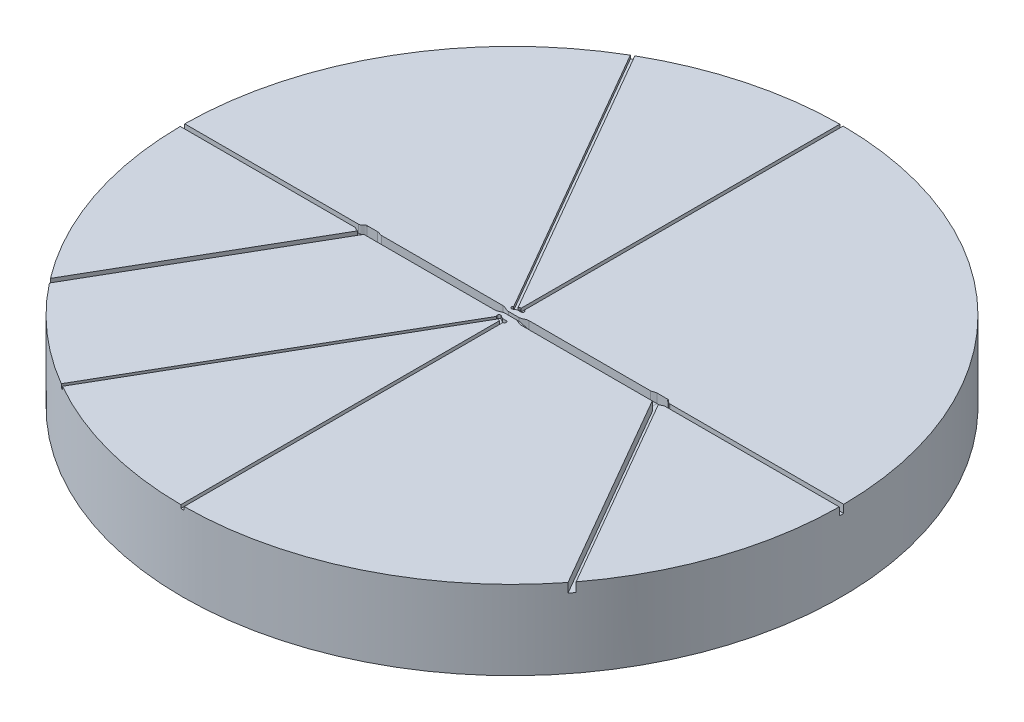
SolidWorks part; units mm, degrees
ref_plane "Front Plane" through (0, 0, 0) normal (0, 0, 1) x (1, 0, 0)
ref_plane "Top Plane" through (0, 0, 0) normal (0, 1, 0) x (1, 0, 0)
ref_plane "Right Plane" through (0, 0, 0) normal (1, 0, 0) x (0, 0, -1)
sketch "Sketch1" plane through (0, 0, 0) normal (0, 1, 0) x (1, 0, 0)
  circle A0 centre (0, 0) radius 12.5
extrude "Boss-Extrude1" add sketch "Sketch1" against normal blind 3
sketch "Sketch2" plane through (0, -3, 0) normal (0, -1, 0) x (-1, 0, 0)
  line L1 (0, 14) -> (14, 14)
  line L2 (0, 14) -> (0, -14)
  line L3 (0, -14) -> (14, -14)
  line L4 (14, 14) -> (14, -14)
extrude "Cut-Extrude1" cut sketch "Sketch2" against normal blind 3
sketch "Sketch4" plane through (0, 0, 0) normal (-1, 0, 0) x (0, 0, 1)
  line L1 (-0.0625, 0.125) -> (0.0625, 0.125)
  line L2 (-0.0625, 0.125) -> (-0.0625, -0.125)
  line L3 (-0.0625, -0.125) -> (0.0625, -0.125)
  line L4 (0.0625, 0.125) -> (0.0625, -0.125)
  line L5 (-0.0625, 0.125) -> (0.0625, -0.125) construction
  line L6 (-0.0625, -0.125) -> (0.0625, 0.125) construction
  point P0 (0, 0)
extrude "Cut-Extrude2" cut sketch "Sketch4" against normal blind 0.2
ref_plane "Plane1" through (0.5, 0, 0) normal (-1, 0, 0) x (0, 0, 1)
sketch "Sketch5" plane through (0.5, 0, 0) normal (-1, 0, 0) x (0, 0, 1)
  line L1 (-0.15, 0.3) -> (0.15, 0.3)
  line L2 (-0.15, 0.3) -> (-0.15, -0.3)
  line L3 (-0.15, -0.3) -> (0.15, -0.3)
  line L4 (0.15, 0.3) -> (0.15, -0.3)
  line L5 (-0.15, 0.3) -> (0.15, -0.3) construction
  line L6 (-0.15, -0.3) -> (0.15, 0.3) construction
  point P1 (0, 0)
extrude "Cut-Extrude3" cut sketch "Sketch5" against normal blind 5
sketch "Sketch7" plane through (0.2, 0, 0) normal (-1, 0, 0) x (0, 0, 1)
  line L1 (-0.0625, 0) -> (0.0625, 0)
  line L2 (-0.0625, 0) -> (-0.0625, -0.125)
  line L3 (-0.0625, -0.125) -> (0.0625, -0.125)
  line L4 (0.0625, 0) -> (0.0625, -0.125)
sketch "Sketch8" plane through (0.5, 0, 0) normal (-1, 0, 0) x (0, 0, 1)
  line L1 (-0.15, 0) -> (0.15, 0)
  line L2 (-0.15, 0) -> (-0.15, -0.3)
  line L3 (-0.15, -0.3) -> (0.15, -0.3)
  line L4 (0.15, 0) -> (0.15, -0.3)
loft "Cut-Loft3" cut profiles "Sketch7", "Sketch8" start constraint normal to profile start tangent length 1 end constraint normal to profile end tangent length 1 connector at (0.2, 0, 0.0625) connector at (0.5, 0, 0.15)
ref_point "Point1"
ref_axis "Axis1" through (0, 0, 0) along (1, 0, 0)
ref_plane "Plane2" through (5.5, 0, 0) normal (-1, 0, 0) x (0, 0, 1)
sketch "Sketch9" plane through (0, 0, 0) normal (0, 1, 0) x (1, 0, 0)
  line L0 (5.5, 0) -> (10.5, -8.6603)
  line L1 (5.5, 0.15) -> (5.5, -0.15) construction
ref_plane "Plane3" through (5.5, 0, 0) normal (0.5, 0, 0.866) x (0.866, 0, -0.5)
ref_plane "Plane4" through (1.425, 0, 2.4682) normal (0.5, 0, 0.866) x (0.866, 0, -0.5)
sketch "Sketch15" plane through (1.425, 0, 2.4682) normal (0.5, 0, 0.866) x (0.866, 0, -0.5)
  line L0 (0, 0) -> (4.7631, 0) construction
  line L1 (4.6631, -0.35) -> (4.8651, -0.35)
  line L2 (4.6631, -0.35) -> (4.6631, 0)
  line L3 (4.6631, 0) -> (4.8651, 0)
  line L4 (4.8651, -0.35) -> (4.8651, 0)
  line L5 (4.6631, -0.35) -> (4.8651, 0) construction
  line L6 (4.6631, 0) -> (4.8651, -0.35) construction
  point P0 (4.7641, -0.175)
extrude "Cut-Extrude4" cut sketch "Sketch15" along normal blind 10
sketch "Sketch20" plane through (5.5, 0, 0) normal (-1, 0, 0) x (0, 0, 1)
  line L1 (-0.2, 0) -> (0.15, 0)
  line L2 (-0.2, 0) -> (-0.2, -0.35)
  line L3 (-0.2, -0.35) -> (0.15, -0.35)
  line L4 (0.15, 0) -> (0.15, -0.35)
  line L5 (-0.2, 0) -> (0.15, -0.35) construction
  line L6 (-0.2, -0.35) -> (0.15, 0) construction
  point P0 (-0.025, -0.175)
extrude "Cut-Extrude7" cut sketch "Sketch20" against normal blind 0.2 and the other way blind 0.2
ref_plane "Plane5" through (5.1, 0, 0) normal (-1, 0, 0) x (0, 0, 1)
sketch "Sketch21" plane through (5.1, 0, 0) normal (-1, 0, 0) x (0, 0, 1)
  line L0 (-0.0625, 0) -> (-12.5, 0) construction
  line L1 (-0.15, 0) -> (0.15, 0)
  line L2 (-0.15, 0) -> (-0.15, -0.3)
  line L3 (-0.15, -0.3) -> (0.15, -0.3)
  line L4 (0.15, 0) -> (0.15, -0.3)
sketch "Sketch22" plane through (5.3, 0, 0) normal (1, 0, 0) x (0, 0, -1)
  line L1 (-0.15, 0) -> (0.2, 0)
  line L2 (-0.15, 0) -> (-0.15, -0.35)
  line L3 (-0.15, -0.35) -> (0.2, -0.35)
  line L4 (0.2, 0) -> (0.2, -0.35)
loft "Cut-Loft4" cut profiles "Sketch22", "Sketch21" start constraint normal to profile start tangent length 1 end constraint normal to profile end tangent length 1 connector at (5.3, 0, 0.15) connector at (5.1, 0, 0.15)
ref_plane "Plane6" through (5.9, 0, 0) normal (-1, 0, 0) x (0, 0, 1)
sketch "Sketch23" plane through (5.9, 0, 0) normal (-1, 0, 0) x (0, 0, 1)
  line L0 (-0.0625, 0) -> (-12.5, 0) construction
  line L1 (-0.085, 0) -> (0.085, 0)
  line L2 (-0.085, 0) -> (-0.085, -0.3)
  line L3 (-0.085, -0.3) -> (0.085, -0.3)
  line L4 (0.085, 0) -> (0.085, -0.3)
sketch "Sketch24" plane through (5.7, 0, 0) normal (-1, 0, 0) x (0, 0, 1)
  line L1 (0.15, 0) -> (-0.2, 0)
  line L2 (0.15, 0) -> (0.15, -0.35)
  line L3 (0.15, -0.35) -> (-0.2, -0.35)
  line L4 (-0.2, 0) -> (-0.2, -0.35)
loft "Cut-Loft5" cut profiles "Sketch24", "Sketch23" start constraint normal to profile start tangent length 1 end constraint normal to profile end tangent length 1 connector at (5.7, 0, -0.2) connector at (5.9, 0, -0.085)
extrude "Cut-Extrude8" cut sketch "Sketch23<2>" against normal blind 8
sketch "Sketch23<2>" plane through (5.9, 0, 0) normal (-1, 0, 0) x (0, 0, 1) same geometry as "Sketch23"
mirror "Mirror1" about plane through (0, 0, 0) normal (1, 0, 0) of bodies 113
ref_plane "Plane7" through (0, 0, 0.3625) normal (0, 0, -1) x (-1, 0, 0)
sketch "Sketch26" plane through (0, 0, 0.3625) normal (0, 0, -1) x (-1, 0, 0)
  line L1 (-0.0625, 0) -> (0.0625, 0)
  line L2 (-0.0625, 0) -> (-0.0625, -0.125)
  line L3 (-0.0625, -0.125) -> (0.0625, -0.125)
  line L4 (0.0625, 0) -> (0.0625, -0.125)
  line L5 (-0.0625, 0) -> (0.0625, -0.125) construction
  line L6 (-0.0625, -0.125) -> (0.0625, 0) construction
  point P0 (0, -0.0625)
extrude "Cut-Extrude9" cut sketch "Sketch26" against normal blind 13
sketch "Sketch27" plane through (0, 0, 0) normal (0, 1, 0) x (1, 0, 0)
  line L0 (0, 0) -> (-1.6943, -2.9346)
ref_plane "Plane8" through (0, 0, 0) normal (-0.5, 0, 0.866) x (0.866, 0, 0.5)
ref_point "Point2"
ref_plane "Plane9" through (-0.1726, 0, 0.2989) normal (-0.5, 0, 0.866) x (0.866, 0, 0.5)
sketch "Sketch28" plane through (-0.1726, 0, 0.2989) normal (-0.5, 0, 0.866) x (0.866, 0, 0.5)
  line L1 (-0.0625, 0) -> (0.0625, 0)
  line L2 (-0.0625, 0) -> (-0.0625, -0.125)
  line L3 (-0.0625, -0.125) -> (0.0625, -0.125)
  line L4 (0.0625, 0) -> (0.0625, -0.125)
  line L5 (-0.0625, 0) -> (0.0625, -0.125) construction
  line L6 (-0.0625, -0.125) -> (0.0625, 0) construction
  point P0 (0, -0.0625)
extrude "Cut-Extrude10" cut sketch "Sketch28" along normal blind 13
sketch "Sketch32" plane through (0, 0, 0) normal (0, 1, 0) x (1, 0, 0)
  line L0 (-0.2267, -0.2677) -> (-0.0941, -0.3443) construction
  line L1 (-1.7866, 0.6329) -> (1.4414, -1.2308) construction
  line L2 (-6.304, -10.7939) -> (-0.2267, -0.2677) construction
  line L3 (-0.1955, -0.2136) -> (-0.0773, -0.2818)
  line L4 (-0.258, -0.3218) -> (-0.1253, -0.3984)
  line L5 (-0.0941, -0.3443) -> (0.0625, -0.3443) construction
  line L6 (-0.0773, -0.2818) -> (0.0625, -0.2818)
  line L7 (-0.0941, -0.4068) -> (0.0625, -0.4068)
  line L19 (-0.2267, -0.2677) -> (-0.1185, -0.3302)
  line L20 (-0.1185, -0.3302) -> (-6.1958, -10.8564)
  line L21 (-0.0625, -12.4998) -> (-0.0625, -0.3625)
  line L22 (-0.0625, -0.3625) -> (0.0625, -0.3625)
  line L23 (0.0625, -0.3625) -> (0.0625, -12.4998)
  line L24 (9.8372, -7.7123) -> (5.4711, -0.15)
  line L25 (5.4711, -0.15) -> (0.5, -0.15)
  line L26 (0.2, -0.0625) -> (-0.2, -0.0625)
  line L27 (-0.5, -0.15) -> (-5.4711, -0.15)
  line L28 (-5.4711, -0.15) -> (-9.8372, -7.7123)
  line L29 (-6.304, -10.7939) -> (-0.2267, -0.2677)
  line L30 (-0.2267, -0.2677) -> (-0.1185, -0.3302)
  line L31 (-0.1185, -0.3302) -> (-6.1958, -10.8564)
  line L32 (-0.0625, -12.4998) -> (-0.0625, -0.3625)
  line L33 (-0.0625, -0.3625) -> (0.0625, -0.3625)
  line L34 (0.0625, -0.3625) -> (0.0625, -12.4998)
  line L35 (9.8372, -7.7123) -> (5.4711, -0.15)
  line L36 (5.4711, -0.15) -> (0.5, -0.15)
  line L37 (0.2, -0.0625) -> (-0.2, -0.0625)
  line L38 (-0.5, -0.15) -> (-5.4711, -0.15)
  line L39 (-5.4711, -0.15) -> (-9.8372, -7.7123)
  line L40 (-6.304, -10.7939) -> (-0.2267, -0.2677)
  arc A0 (-0.1955, -0.2136) -> (-0.258, -0.3218) centre (-0.2267, -0.2677) ccw
  arc A1 (-0.1253, -0.3984) -> (-0.0941, -0.4068) centre (-0.0941, -0.3443) ccw
  arc A3 (0.0625, -0.4068) -> (0.0625, -0.2818) centre (0.0625, -0.3443) ccw
  arc A7 (-6.1958, -10.8564) -> (-0.0625, -12.4998) centre (0, 0) ccw
  arc A8 (0.0625, -12.4998) -> (9.8372, -7.7123) centre (0, 0) ccw
  arc A9 (-9.8372, -7.7123) -> (-6.304, -10.7939) centre (0, 0) ccw
  arc A10 (-6.1958, -10.8564) -> (-0.0625, -12.4998) centre (0, 0) ccw
  arc A11 (0.0625, -12.4998) -> (9.8372, -7.7123) centre (0, 0) ccw
  arc A12 (-9.8372, -7.7123) -> (-6.304, -10.7939) centre (0, 0) ccw
  spline S2 degree 3 poles (432.4643, 2968.4664) (-421.6991, -2973.1923) (422.4012, 2972.995) (-431.7709, -2968.7245) knots -25.204015 -25.204015 -25.204015 -25.204015 26.204147 26.204147 26.204147 26.204147 only from (0.5, -0.15) to (0.2, -0.0625)
  spline S3 degree 3 poles (431.7643, -2968.6789) (-422.3991, 2972.9798) (421.7012, -2973.2075) (-432.4709, 2968.512) knots -25.204015 -25.204015 -25.204015 -25.204015 26.204147 26.204147 26.204147 26.204147 only from (-0.2, -0.0625) to (-0.5, -0.15)
  spline S4 degree 3 poles (0.5, -0.15) (0.3958, -0.15) (0.3042, -0.0625) (0.2, -0.0625) knots 0 0 0 0 1 1 1 1
  spline S5 degree 3 poles (-0.2, -0.0625) (-0.3042, -0.0625) (-0.3958, -0.15) (-0.5, -0.15) knots 0 0 0 0 1 1 1 1
  point P6 (-0.1604, -0.306)
  point P13 (-0.0158, -0.3443)
  dimension "D1" = 0
extrude "Cut-Extrude16" cut sketch "Sketch32" against normal blind 0.125 contours A3 L6 L3 A0 L36 L4 A1 L7 region at (-0.0775, 0, 0.3102)
mirror "Mirror2" about plane through (0, 0, 0) normal (0, 0, 1) of "Cut-Extrude16", "Cut-Extrude10", "Cut-Extrude9"
